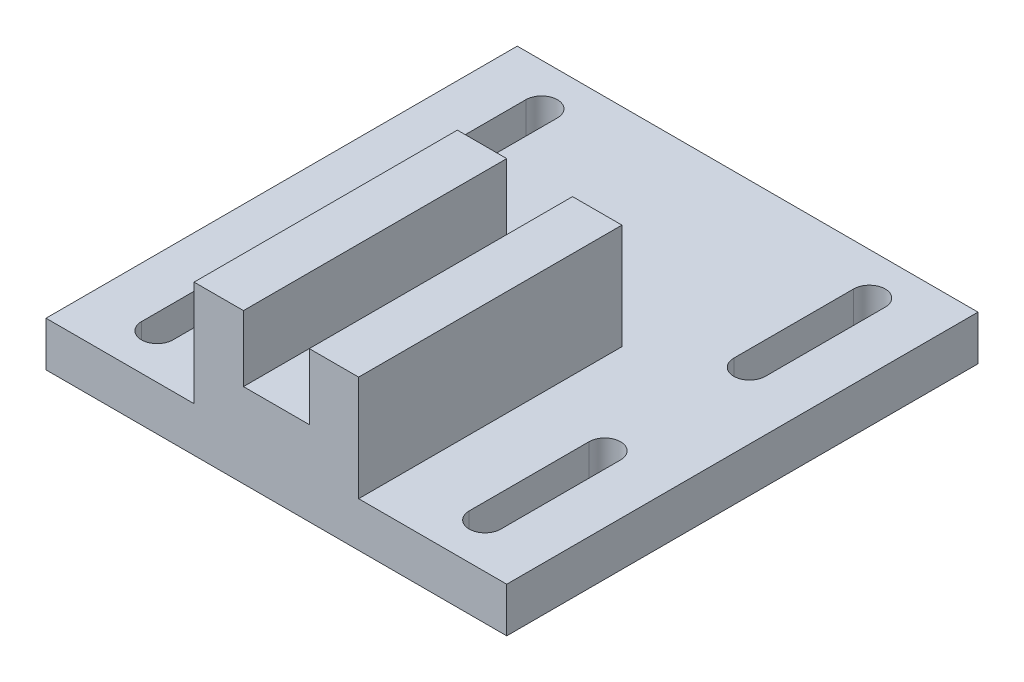
SolidWorks part; units mm, degrees
material "6061 Alloy"
ref_plane "Front Plane" through (0, 0, 0) normal (0, 0, 1) x (1, 0, 0)
ref_plane "Top Plane" through (0, 0, 0) normal (0, 1, 0) x (1, 0, 0)
ref_plane "Right Plane" through (0, 0, 0) normal (1, 0, 0) x (0, 0, -1)
sketch "Sketch1" plane through (0, 0, 0) normal (0, 1, 0) x (1, 0, 0)
  line L0 (6.4135, -4.064) -> (6.4135, -15.621) construction
  line L1 (0, 0) -> (44.45, 0)
  line L2 (0, 0) -> (0, -45.466)
  line L3 (0, -45.466) -> (44.45, -45.466)
  line L4 (44.45, 0) -> (44.45, -45.466)
  line L5 (14.2875, -45.466) -> (30.1625, -45.466)
  line L6 (14.2875, -45.466) -> (14.2875, -20.066)
  line L7 (14.2875, -20.066) -> (30.1625, -20.066)
  line L8 (30.1625, -45.466) -> (30.1625, -20.066)
  line L9 (7.9375, -4.064) -> (7.9375, -15.621)
  line L10 (4.8895, -4.064) -> (4.8895, -15.621)
  line L11 (6.4135, -29.591) -> (6.4135, -41.148) construction
  line L12 (7.9375, -29.591) -> (7.9375, -41.148)
  line L13 (4.8895, -29.591) -> (4.8895, -41.148)
  line L14 (38.0365, -4.064) -> (38.0365, -15.621) construction
  line L15 (39.5605, -4.064) -> (39.5605, -15.621)
  line L16 (36.5125, -4.064) -> (36.5125, -15.621)
  line L17 (38.0365, -29.591) -> (38.0365, -41.148) construction
  line L18 (39.5605, -29.591) -> (39.5605, -41.148)
  line L19 (36.5125, -29.591) -> (36.5125, -41.148)
  line L20 (6.4135, -4.064) -> (38.0365, -4.064) construction
  line L21 (38.0365, -2.54) -> (38.0365, -17.145) construction
  line L22 (38.0365, -42.672) -> (38.0365, -45.466) construction
  arc A0 (7.9375, -4.064) -> (4.8895, -4.064) centre (6.4135, -4.064) ccw
  arc A1 (4.8895, -15.621) -> (7.9375, -15.621) centre (6.4135, -15.621) ccw
  arc A2 (7.9375, -29.591) -> (4.8895, -29.591) centre (6.4135, -29.591) ccw
  arc A3 (4.8895, -41.148) -> (7.9375, -41.148) centre (6.4135, -41.148) ccw
  arc A4 (39.5605, -4.064) -> (36.5125, -4.064) centre (38.0365, -4.064) ccw
  arc A5 (36.5125, -15.621) -> (39.5605, -15.621) centre (38.0365, -15.621) ccw
  arc A6 (39.5605, -29.591) -> (36.5125, -29.591) centre (38.0365, -29.591) ccw
  arc A7 (36.5125, -41.148) -> (39.5605, -41.148) centre (38.0365, -41.148) ccw
  point P9 (22.225, -20.066)
  point P10 (22.225, 0)
  point P13 (6.4135, -9.8425)
  point P18 (6.4135, -35.3695)
  point P27 (38.0365, -9.8425)
  point P32 (38.0365, -35.3695)
  point P41 (22.225, -4.064)
  point P44 (38.0365, -28.067)
  point P47 (8.8905, -14.668)
  dimension "D1" = 44.45
  dimension "D2" = 45.466
  dimension "D3" = 15.875
  dimension "D4" = 25.4
  dimension "D5" = 31.623
  dimension "D6" = 14.605
  dimension "D7" = 2.794
  dimension "D8" = 10.922
  dimension "D9" = 3.048
extrude "Boss-Extrude1" add sketch "Sketch1" along normal blind 4.318 contours L8 L3 L4 L1 L2 L6 L7 A7 L19 A6 L18 A5 L16 A4 L15 A3 L13 A2 L12 A1 L10 A0 L9 | L3 L8 L7 L6 region at (22.225, 0, 19.9534) region at (22.225, 0, 32.766)
extrude "Boss-Extrude2" add sketch "Sketch1<3>" along normal blind 10.16 from surface contours L3 L8 L7 L6 region at (22.225, 0, 32.766) starting at face at (38.0365, 4.318, 35.3695)
sketch "Sketch1<3>" plane through (0, 0, 0) normal (0, 1, 0) x (1, 0, 0) same geometry as "Sketch1"
sketch "Sketch2" plane through (0, 0, 45.466) normal (0, 0, 1) x (1, 0, 0)
  line L0 (30.1625, 14.478) -> (14.2875, 14.478) construction
  line L1 (25.4, 14.478) -> (19.05, 14.478)
  line L2 (25.4, 14.478) -> (25.4, 8.128)
  line L3 (25.4, 8.128) -> (19.05, 8.128)
  line L4 (19.05, 14.478) -> (19.05, 8.128)
  point P6 (22.225, 14.478)
  point P7 (22.225, 14.478)
  dimension "D1" = 6.35
  dimension "D2" = 6.35
extrude "Cut-Extrude1" cut sketch "Sketch2" against normal through all both and the other way through all
